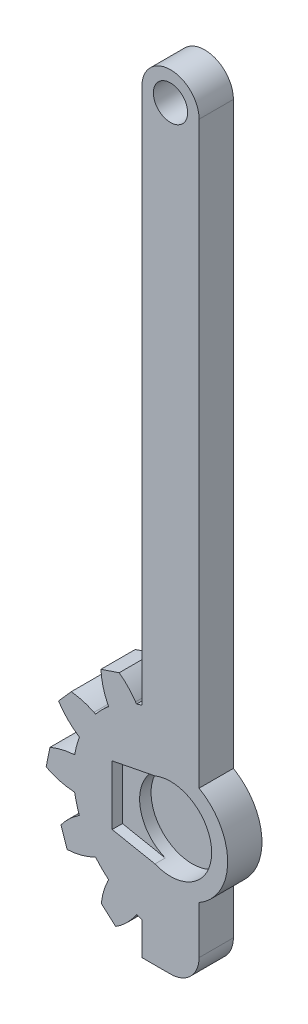
SolidWorks part; units mm, degrees
ref_plane "Front Plane" through (0, 0, 0) normal (0, 0, 1) x (1, 0, 0)
ref_plane "Top Plane" through (0, 0, 0) normal (0, 1, 0) x (1, 0, 0)
ref_plane "Right Plane" through (0, 0, 0) normal (1, 0, 0) x (0, 0, -1)
ref_plane "Plane1" through (0, 0, 1.9) normal (0, 0, 1) x (1, 0, 0)
sketch "Sketch1" plane through (0, 0, 1.9) normal (0, 0, 1) x (1, 0, 0)
  line L0 (2.5, -11) -> (2.5, -4.3301)
  line L1 (2.5, 4.3301) -> (2.5, 55)
  line L2 (-2.5, 55) -> (-2.5, 8.124)
  line L3 (-2.9677, 7.9651) -> (-3.0542, 8.0933)
  line L4 (-5.4819, 6.6916) -> (-5.4141, 6.5527)
  line L5 (-6.5527, 5.4141) -> (-6.6916, 5.4819)
  line L6 (-8.0933, 3.0542) -> (-7.9651, 2.9677)
  line L7 (-8.3818, 1.4124) -> (-8.5361, 1.4016)
  line L8 (-8.5361, -1.4016) -> (-8.3818, -1.4124)
  line L9 (-7.9651, -2.9677) -> (-8.0933, -3.0542)
  line L10 (-6.6916, -5.4819) -> (-6.5527, -5.4141)
  line L11 (-5.4141, -6.5527) -> (-5.4819, -6.6916)
  line L12 (-3.0542, -8.0933) -> (-2.9677, -7.9651)
  line L13 (-2.5, -8.124) -> (-2.5, -11)
  line L14 (-2.5, -11) -> (2.5, -11)
  arc A0 (2.5, -4.3301) -> (2.5, 4.3301) centre (0, 0) ccw
  arc A1 (2.5, 55) -> (-2.5, 55) centre (0, 55) ccw
  arc A2 (-2.5, 8.124) -> (-2.9677, 7.9651) centre (0, 0) ccw
  arc A3 (-3.0542, 8.0933) -> (-5.9946, 10.3829) centre (-8.0284, 4.7381) ccw
  arc A4 (-5.9946, 10.3829) -> (-5.4819, 6.6916) centre (-0.0891, 9.3218) ccw
  arc A5 (-5.4141, 6.5527) -> (-6.5527, 5.4141) centre (0, 0) ccw
  arc A6 (-6.6916, 5.4819) -> (-10.3829, 5.9946) centre (-9.3218, 0.0891) ccw
  arc A7 (-10.3829, 5.9946) -> (-8.0933, 3.0542) centre (-4.7381, 8.0284) ccw
  arc A8 (-7.9651, 2.9677) -> (-8.3818, 1.4124) centre (0, 0) ccw
  arc A9 (-8.5361, 1.4016) -> (-11.9891, 0) centre (-8.1175, -4.5837) ccw
  arc A10 (-11.9891, 0) -> (-8.5361, -1.4016) centre (-8.1175, 4.5837) ccw
  arc A11 (-8.3818, -1.4124) -> (-7.9651, -2.9677) centre (0, 0) ccw
  arc A12 (-8.0933, -3.0542) -> (-10.3829, -5.9946) centre (-4.7381, -8.0284) ccw
  arc A13 (-10.3829, -5.9946) -> (-6.6916, -5.4819) centre (-9.3218, -0.0891) ccw
  arc A14 (-6.5527, -5.4141) -> (-5.4141, -6.5527) centre (0, 0) ccw
  arc A15 (-5.4819, -6.6916) -> (-5.9946, -10.3829) centre (-0.0891, -9.3218) ccw
  arc A16 (-5.9946, -10.3829) -> (-3.0542, -8.0933) centre (-8.0284, -4.7381) ccw
  arc A17 (-2.9677, -7.9651) -> (-2.5, -8.124) centre (0, 0) ccw
  circle A18 centre (0, 55) radius 1.5
  dimension "D1" = 5
  dimension "D2" = 0.0891
  dimension "D3" = 8.5
  dimension "D4" = 6
  dimension "D13" = 3
  dimension "D5" = 2.9677
  dimension "D6" = 3.0542
  dimension "D7" = 4.7381
  dimension "D8" = 5.4141
  dimension "D9" = 5.4819
  dimension "D10" = 6.5527
  dimension "D11" = 8.1175
  dimension "D12" = 8.3818
  dimension "D14" = 11
  dimension "D15" = 55
extrude "Boss-Extrude1" add sketch "Sketch1" against normal blind 3
ref_plane "Plane2" through (0, 0, 1.9) normal (0, 0, -1) x (-1, 0, 0)
sketch "Sketch4" plane through (0, 0, 1.9) normal (0, 0, 1) x (1, 0, 0)
  line L0 (-5.1029, -2.6) -> (-1.3588, -3.3337)
  line L1 (-1.3588, 3.3337) -> (-5.1029, 2.6)
  line L2 (-5.1029, 2.6) -> (-5.1029, -2.6)
  arc A0 (-1.3588, -3.3337) -> (-1.3588, 3.3337) centre (0, 0) cw
extrude "Cut-Extrude2" cut sketch "Sketch4" against normal blind 0.9
sketch "Sketch5" plane through (0, 0, 0) normal (0, 1, 0) x (1, 0, 0)
  line L0 (3.6, 0) -> (0, 0)
  line L1 (0, 0) -> (0, -3)
  line L2 (0, -3) -> (3.6, -3)
  line L3 (3.6, -3) -> (3.6, 0)
  line L4 (0, 0) -> (0, -3) construction
revolve "Cut-Revolve1" cut sketch "Sketch5" angle 360 about L4 reverse direction yes
chamfer "Chamfer1" distance 1.4124 angle 61.288 5 edges at (-10.3829, -5.9946, 0.4) (-5.9946, -10.3829, 0.4) (-11.9891, 0, 0.4) (-10.3829, 5.9946, 0.4) (-5.9946, 10.3829, 0.4) first distance on face at (-8.5169, -5.8852, 0.4) first distance on face at (-4.4332, -9.3551, 0.4) first distance on face at (-10.3184, -0.8383, 0.4) first distance on face at (-9.3551, 4.4332, 0.4) first distance on face at (-5.8852, 8.5169, 0.4)
fillet "Fillet1" radius 2.5 1 edges at (2.5, -11, 0.4) tangent propagation no
